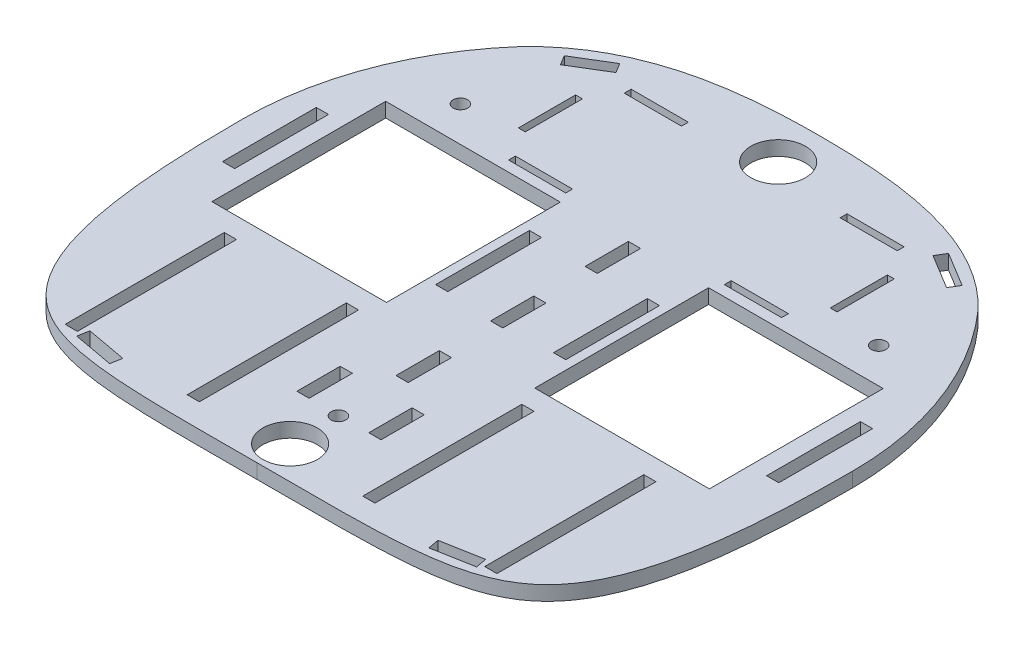
SolidWorks part; units mm, degrees
ref_plane "Front Plane" through (0, 0, 0) normal (0, 0, 1) x (1, 0, 0)
ref_plane "Top Plane" through (0, 0, 0) normal (0, 1, 0) x (1, 0, 0)
ref_plane "Right Plane" through (0, 0, 0) normal (1, 0, 0) x (0, 0, -1)
sketch "Sketch1" plane through (0, 0, 0) normal (0, 1, 0) x (1, 0, 0)
  line L0 (0, 0) -> (-157.9039, -157.9039) construction
  line L1 (0, -127) -> (0, 133.35) construction
  arc A0 (133.35, 0) -> (-133.35, 0) centre (0, 0) ccw
  spline S0 degree 3 poles (-133.35, 0) (-133.35, -51.198) (-123.8034, -129.8051) (-58.428, -127) (0, -127) knots 0 0 0 0 0.502616 1 1 1 1
  spline S1 degree 3 poles (133.35, 0) (133.35, -51.198) (123.8034, -129.8051) (58.428, -127) (0, -127) knots 0 0 0 0 0.502616 1 1 1 1
  dimension "D1" = 266.7
extrude "Base" add sketch "Sketch1" along normal blind 6.35
sketch "ShaftLayout" plane through (0, 6.35, 0) normal (0, 1, 0) x (1, 0, 0)
  line L0 (-133.35, 0) -> (133.35, 0) construction
  line L1 (0, 133.35) -> (0, -127) construction
  line L2 (-114.7053, -6.35) -> (-104.7993, -6.35)
  line L3 (-36.3853, -38) -> (-94.3853, -38)
  line L4 (-36.3853, -38) -> (-36.3853, 38)
  line L5 (-36.3853, 38) -> (-94.3853, 38)
  line L6 (-94.3853, -38) -> (-94.3853, 38)
  line L7 (-36.3853, -38) -> (-94.3853, 38) construction
  line L8 (-36.3853, 38) -> (-94.3853, -38) construction
  line L9 (-102.0053, -15.875) -> (-104.7993, -15.875)
  line L10 (-102.0053, -15.875) -> (-102.0053, 15.875)
  line L11 (-102.0053, 15.875) -> (-104.7993, 15.875)
  line L12 (-104.7993, -15.875) -> (-104.7993, 15.875)
  line L13 (-102.0053, -15.875) -> (-104.7993, 15.875) construction
  line L14 (-102.0053, 15.875) -> (-104.7993, -15.875) construction
  line L15 (-114.7053, -6.35) -> (-114.7053, 6.35)
  line L16 (-104.7993, -6.35) -> (-104.7993, 6.35)
  line L17 (-114.7053, 6.35) -> (-104.7993, 6.35)
  line L18 (-114.7053, -6.35) -> (-104.7993, 6.35) construction
  line L19 (-104.7993, -6.35) -> (-114.7053, 6.35) construction
  line L20 (-116.2928, -9.525) -> (-114.7053, -9.525)
  line L21 (-116.2928, -9.525) -> (-116.2928, 9.525)
  line L22 (-114.7053, -9.525) -> (-114.7053, 9.525)
  line L23 (-116.2928, 9.525) -> (-114.7053, 9.525)
  line L24 (-116.2928, -9.525) -> (-114.7053, 9.525) construction
  line L25 (-114.7053, -9.525) -> (-116.2928, 9.525) construction
  line L26 (-127.4053, -7.9375) -> (-116.2928, -7.9375)
  line L27 (-127.4053, -7.9375) -> (-127.4053, 7.9375)
  line L28 (-116.2928, -7.9375) -> (-116.2928, 7.9375)
  line L29 (-127.4053, 7.9375) -> (-116.2928, 7.9375)
  line L30 (-127.4053, -7.9375) -> (-116.2928, 7.9375) construction
  line L31 (-116.2928, -7.9375) -> (-127.4053, 7.9375) construction
  line L32 (-17.3353, -7.9375) -> (-28.4478, -7.9375)
  line L33 (-30.0353, -9.525) -> (-28.4478, -9.525)
  line L34 (-30.0353, -9.525) -> (-30.0353, 9.525)
  line L35 (-30.0353, 9.525) -> (-28.4478, 9.525)
  line L36 (-28.4478, -9.525) -> (-28.4478, 9.525)
  line L37 (-30.0353, -9.525) -> (-28.4478, 9.525) construction
  line L38 (-30.0353, 9.525) -> (-28.4478, -9.525) construction
  line L39 (-17.3353, -7.9375) -> (-17.3353, 7.9375)
  line L40 (-28.4478, -7.9375) -> (-28.4478, 7.9375)
  line L41 (-17.3353, 7.9375) -> (-28.4478, 7.9375)
  line L42 (-17.3353, -7.9375) -> (-28.4478, 7.9375) construction
  line L43 (-28.4478, -7.9375) -> (-17.3353, 7.9375) construction
  line L45 (-67.3853, -10.033) -> (-56.3853, -10.033)
  line L46 (-67.3853, -10.033) -> (-67.3853, 10.033)
  line L47 (-67.3853, 10.033) -> (-56.3853, 10.033)
  line L48 (-56.3853, -10.033) -> (-56.3853, 10.033)
  line L49 (-67.3853, -10.033) -> (-56.3853, 10.033) construction
  line L50 (-67.3853, 10.033) -> (-56.3853, -10.033) construction
  arc A0 (133.35, 0) -> (-133.35, 0) centre (0, 0) ccw construction
  point P10 (-65.3853, 0)
  point P15 (-103.4023, 0)
  point P20 (-29.2416, 0)
  point P21 (-109.7523, 0)
  point P22 (-115.4991, 0)
  point P23 (-121.8491, 0)
  point P40 (-61.8853, 0)
  point P41 (-22.8916, 0)
  dimension "D1" = 58
  dimension "D2" = 76
  dimension "D3" = 7.62
  dimension "D4" = 2.794
  dimension "D5" = 31.75
  dimension "D6" = 9.906
  dimension "D7" = 12.7
  dimension "D8" = 19.05
  dimension "D9" = 1.5875
  dimension "D10" = 12.7
  dimension "D11" = 15.875
  dimension "D12" = 19.05
  dimension "D13" = 1.5875
  dimension "D14" = 15.875
  dimension "D15" = 12.7
  dimension "D16" = 6.35
  dimension "D17" = 20.066
  dimension "D18" = 20
  dimension "D19" = 11
sketch "MotorLayout" plane through (0, 6.35, 0) normal (0, 1, 0) x (1, 0, 0)
  line L0 (-94.3853, -81.74) -> (-114.3853, -81.74) construction
  line L1 (-94.3853, -110.24) -> (-18.3853, -110.24)
  line L2 (-94.3853, -110.24) -> (-94.3853, -53.24)
  line L3 (-94.3853, -53.24) -> (-18.3853, -53.24)
  line L4 (-18.3853, -110.24) -> (-18.3853, -53.24)
  line L5 (-94.3853, -110.24) -> (-18.3853, -53.24) construction
  line L6 (-94.3853, -53.24) -> (-18.3853, -110.24) construction
  line L7 (-114.7053, -92.0587) -> (-104.7993, -92.0587)
  line L8 (-104.7993, -97.615) -> (-102.0053, -97.615)
  line L9 (-104.7993, -97.615) -> (-104.7993, -65.865)
  line L10 (-104.7993, -65.865) -> (-102.0053, -65.865)
  line L11 (-102.0053, -97.615) -> (-102.0053, -65.865)
  line L12 (-104.7993, -97.615) -> (-102.0053, -65.865) construction
  line L13 (-104.7993, -65.865) -> (-102.0053, -97.615) construction
  line L14 (-36.3853, -38) -> (-94.3853, -38) construction
  line L15 (-114.7053, -92.0587) -> (-114.7053, -71.4212)
  line L16 (-104.7993, -92.0587) -> (-104.7993, -71.4212)
  line L17 (-114.7053, -71.4212) -> (-104.7993, -71.4212)
  line L18 (-114.7053, -92.0587) -> (-104.7993, -71.4212) construction
  line L19 (-104.7993, -92.0587) -> (-114.7053, -71.4212) construction
  line L20 (-103.4023, -1000) -> (-103.4023, 49000) construction
  line L21 (-34.8953, -53.24) -> (-34.8953, -110.24) construction
  point P0 (-56.3853, -81.74)
  point P7 (-103.4023, -81.74)
  point P14 (-109.7523, -81.74)
  dimension "D1" = 20
  dimension "D2" = 76
  dimension "D3" = 57
  dimension "D4" = 2.794
  dimension "D5" = 15.24
  dimension "D6" = 31.75
  dimension "D7" = 20.6375
  dimension "D8" = 12.7
  dimension "D9" = 7.62
  dimension "D10" = 16.51
sketch "Sketch6" plane through (0, 6.35, 0) normal (0, 1, 0) x (1, 0, 0)
  line L0 (-36.3853, -38) -> (-36.3853, 38) construction
  line L1 (-32.4166, -38) -> (-108.7681, -38)
  line L2 (-32.4166, -38) -> (-32.4166, 38)
  line L3 (-32.4166, 38) -> (-108.7681, 38)
  line L4 (-108.7681, -38) -> (-108.7681, 38)
  line L5 (-28.4478, -9.525) -> (-28.4478, 9.525) construction
  line L6 (-104.7993, -15.875) -> (-104.7993, 15.875) construction
  line L7 (0, 133.35) -> (0, -127) construction
  line L8 (28.4478, 20.5105) -> (23.1138, -20.5105) construction
  line L9 (28.4478, -20.5105) -> (23.1138, 20.5105) construction
  line L10 (116.2928, 20.5105) -> (121.6268, -20.5105) construction
  line L11 (116.2928, -20.5105) -> (121.6268, 20.5105) construction
  line L12 (-133.35, 0) -> (133.35, 0) construction
  line L13 (-116.2928, -20.5105) -> (-121.6268, -20.5105)
  line L14 (-116.2928, -20.5105) -> (-116.2928, 20.5105)
  line L15 (-116.2928, 20.5105) -> (-121.6268, 20.5105)
  line L16 (-121.6268, -20.5105) -> (-121.6268, 20.5105)
  line L17 (-116.2928, -20.5105) -> (-121.6268, 20.5105) construction
  line L18 (-116.2928, 20.5105) -> (-121.6268, -20.5105) construction
  line L19 (-116.2928, -9.525) -> (-116.2928, 9.525) construction
  line L20 (-127.4053, 7.9375) -> (-116.2928, 7.9375) construction
  line L21 (-17.3353, 7.9375) -> (-28.4478, 7.9375) construction
  line L22 (-28.4478, -20.5105) -> (-23.1138, -20.5105)
  line L23 (-28.4478, -20.5105) -> (-28.4478, 20.5105)
  line L24 (-28.4478, 20.5105) -> (-23.1138, 20.5105)
  line L25 (-23.1138, -20.5105) -> (-23.1138, 20.5105)
  line L26 (-28.4478, -20.5105) -> (-23.1138, 20.5105) construction
  line L27 (-28.4478, 20.5105) -> (-23.1138, -20.5105) construction
  line L28 (23.1138, -20.5105) -> (23.1138, 20.5105)
  line L29 (28.4478, 20.5105) -> (23.1138, 20.5105)
  line L30 (28.4478, -20.5105) -> (28.4478, 20.5105)
  line L31 (28.4478, -20.5105) -> (23.1138, -20.5105)
  line L32 (121.6268, -20.5105) -> (121.6268, 20.5105)
  line L33 (116.2928, 20.5105) -> (121.6268, 20.5105)
  line L34 (116.2928, -20.5105) -> (116.2928, 20.5105)
  line L35 (116.2928, -20.5105) -> (121.6268, -20.5105)
  line L36 (108.7681, -38) -> (108.7681, 38)
  line L37 (32.4166, 38) -> (108.7681, 38)
  line L38 (32.4166, -38) -> (32.4166, 38)
  line L39 (32.4166, -38) -> (108.7681, -38)
  point P16 (-118.9598, 0)
  point P27 (-25.7808, 0)
  point P44 (25.7808, 0)
  point P45 (118.9598, 0)
  dimension "D1" = 3.9688
  dimension "D2" = 3.9688
  dimension "D3" = 12.573
  dimension "D4" = 12.573
  dimension "D5" = 5.334
  dimension "D6" = 5.334
extrude "WheelShaftCut" cut sketch "Sketch6" against normal through all
sketch "Sketch8" plane through (0, 6.35, 0) normal (0, 1, 0) x (1, 0, 0)
  line L0 (-94.3853, -81.74) -> (-18.3853, -81.74) construction
  line L1 (-18.3853, -110.24) -> (-18.3853, -53.24) construction
  line L2 (-94.3853, -53.24) -> (-18.3853, -53.24) construction
  line L3 (-35.7113, -116.5265) -> (-41.0453, -116.5265)
  line L4 (-35.7113, -116.5265) -> (-35.7113, -46.9535)
  line L5 (-35.7113, -46.9535) -> (-41.0453, -46.9535)
  line L6 (-41.0453, -116.5265) -> (-41.0453, -46.9535)
  line L7 (-35.7113, -116.5265) -> (-41.0453, -46.9535) construction
  line L8 (-35.7113, -46.9535) -> (-41.0453, -116.5265) construction
  line L9 (18.3853, -72.2785) -> (13.0513, -91.2015) construction
  line L10 (18.3853, -91.2015) -> (13.0513, -72.2785) construction
  line L11 (18.3853, -81.74) -> (15.7183, -81.74) construction
  line L12 (89.0513, -46.9535) -> (94.3853, -116.5265) construction
  line L13 (89.0513, -116.5265) -> (94.3853, -46.9535) construction
  line L14 (35.7113, -46.9535) -> (41.0453, -116.5265) construction
  line L15 (-89.0513, -116.5265) -> (-94.3853, -116.5265)
  line L16 (-89.0513, -116.5265) -> (-89.0513, -46.9535)
  line L17 (-89.0513, -46.9535) -> (-94.3853, -46.9535)
  line L18 (-94.3853, -116.5265) -> (-94.3853, -46.9535)
  line L19 (-89.0513, -116.5265) -> (-94.3853, -46.9535) construction
  line L20 (-89.0513, -46.9535) -> (-94.3853, -116.5265) construction
  line L21 (-94.3853, -110.24) -> (-94.3853, -53.24) construction
  line L22 (0, 133.35) -> (0, -127) construction
  line L23 (35.7113, -116.5265) -> (41.0453, -46.9535) construction
  line L24 (94.3853, -81.74) -> (18.3853, -81.74) construction
  line L25 (13.0513, -91.2015) -> (13.0513, -72.2785)
  line L26 (18.3853, -72.2785) -> (13.0513, -72.2785)
  line L27 (18.3853, -91.2015) -> (18.3853, -72.2785)
  line L28 (18.3853, -91.2015) -> (13.0513, -91.2015)
  line L29 (94.3853, -116.5265) -> (94.3853, -46.9535)
  line L30 (89.0513, -46.9535) -> (94.3853, -46.9535)
  line L31 (89.0513, -116.5265) -> (89.0513, -46.9535)
  line L32 (89.0513, -116.5265) -> (94.3853, -116.5265)
  line L33 (41.0453, -116.5265) -> (41.0453, -46.9535)
  line L34 (35.7113, -46.9535) -> (41.0453, -46.9535)
  line L35 (35.7113, -116.5265) -> (35.7113, -46.9535)
  line L36 (35.7113, -116.5265) -> (41.0453, -116.5265)
  line L37 (-94.3853, -110.24) -> (-18.3853, -110.24) construction
  line L42 (-18.3853, -81.74) -> (-15.7183, -81.74) construction
  line L44 (-18.3853, -91.2015) -> (-13.0513, -91.2015)
  line L45 (-18.3853, -91.2015) -> (-18.3853, -72.2785)
  line L46 (-18.3853, -72.2785) -> (-13.0513, -72.2785)
  line L47 (-13.0513, -91.2015) -> (-13.0513, -72.2785)
  line L48 (-18.3853, -91.2015) -> (-13.0513, -72.2785) construction
  line L49 (-18.3853, -72.2785) -> (-13.0513, -91.2015) construction
  point P6 (-63.7079, -81.74)
  point P7 (-38.2513, -81.74)
  point P19 (-91.5913, -81.74)
  point P39 (91.5913, -81.74)
  point P40 (38.2513, -81.74)
  dimension "D1" = 5.334
  dimension "D2" = 6.2865
  dimension "D4" = 5.334
  dimension "D5" = 18.923
  dimension "D6" = 6.2865
  dimension "D3" = 2
extrude "MotorCut" cut sketch "Sketch8" against normal through all
sketch "BatteryLayout" plane through (0, 6.35, 0) normal (0, 1, 0) x (1, 0, 0)
  line L0 (0, 133.35) -> (0, -127) construction
  line L1 (-32.4166, 38) -> (-108.7681, 38) construction
  line L2 (-66.675, 45.62) -> (66.675, 45.62)
  line L3 (-66.675, 45.62) -> (-66.675, 93.245)
  line L4 (-66.675, 93.245) -> (66.675, 93.245)
  line L5 (66.675, 45.62) -> (66.675, 93.245)
  line L6 (-66.675, 45.62) -> (66.675, 93.245) construction
  line L7 (-66.675, 93.245) -> (66.675, 45.62) construction
  arc A0 (133.35, 0) -> (-133.35, 0) centre (0, 0) ccw construction
  point P6 (0, 69.4325)
  dimension "D1" = 133.35
  dimension "D2" = 47.625
  dimension "D3" = 7.62
sketch "Sketch10" plane through (0, 6.35, 0) normal (0, 1, 0) x (1, 0, 0)
  line L0 (-66.675, 93.245) -> (66.675, 93.245) construction
  line L1 (-59.69, 42.62) -> (-34.69, 42.62)
  line L2 (-59.69, 42.62) -> (-59.69, 45.62)
  line L3 (-59.69, 45.62) -> (-34.69, 45.62)
  line L4 (-34.69, 42.62) -> (-34.69, 45.62)
  line L5 (-59.69, 42.62) -> (-34.69, 45.62) construction
  line L6 (-59.69, 45.62) -> (-34.69, 42.62) construction
  line L7 (-59.69, 96.245) -> (-34.69, 96.245)
  line L8 (-59.69, 96.245) -> (-59.69, 93.245)
  line L9 (-59.69, 93.245) -> (-34.69, 93.245)
  line L10 (-34.69, 96.245) -> (-34.69, 93.245)
  line L11 (-59.69, 96.245) -> (-34.69, 93.245) construction
  line L12 (-59.69, 93.245) -> (-34.69, 96.245) construction
  line L13 (-66.675, 45.62) -> (66.675, 45.62) construction
  line L14 (-66.675, 45.62) -> (-66.675, 93.245) construction
  line L15 (0, 69.4325) -> (-66.675, 69.4325) construction
  line L16 (-66.675, 56.9325) -> (-69.675, 56.9325)
  line L17 (-66.675, 56.9325) -> (-66.675, 81.9325)
  line L18 (-66.675, 81.9325) -> (-69.675, 81.9325)
  line L19 (-69.675, 56.9325) -> (-69.675, 81.9325)
  line L20 (0, 133.35) -> (0, -127) construction
  line L21 (59.69, 93.245) -> (34.69, 96.245) construction
  line L22 (59.69, 96.245) -> (34.69, 93.245) construction
  line L23 (59.69, 45.62) -> (34.69, 42.62) construction
  line L24 (59.69, 42.62) -> (34.69, 45.62) construction
  line L25 (69.675, 56.9325) -> (69.675, 81.9325)
  line L26 (66.675, 81.9325) -> (69.675, 81.9325)
  line L27 (66.675, 56.9325) -> (66.675, 81.9325)
  line L28 (66.675, 56.9325) -> (69.675, 56.9325)
  line L29 (34.69, 96.245) -> (34.69, 93.245)
  line L30 (59.69, 93.245) -> (34.69, 93.245)
  line L31 (59.69, 96.245) -> (59.69, 93.245)
  line L32 (59.69, 96.245) -> (34.69, 96.245)
  line L33 (34.69, 42.62) -> (34.69, 45.62)
  line L34 (59.69, 45.62) -> (34.69, 45.62)
  line L35 (59.69, 42.62) -> (59.69, 45.62)
  line L36 (59.69, 42.62) -> (34.69, 42.62)
  point P0 (-47.19, 44.12)
  point P5 (-47.19, 94.745)
  point P20 (-66.675, 69.4325)
  point P40 (66.675, 69.4325)
  point P41 (47.19, 94.745)
  point P42 (47.19, 44.12)
  dimension "D1" = 3
  dimension "D2" = 3
  dimension "D3" = 25
  dimension "D4" = 25
  dimension "D5" = 6.985
  dimension "D6" = 6.985
  dimension "D7" = 3
  dimension "D8" = 25
extrude "VelcroCut" cut sketch "Sketch10" against normal through all
sketch "Sketch11" plane through (0, 6.35, 0) normal (0, 1, 0) x (1, 0, 0)
  line L0 (0, 133.35) -> (0, -127) construction
  line L1 (-133.35, 0) -> (133.35, 0) construction
  circle A1 centre (0, -91.44) radius 3.175
  circle A2 centre (-91.44, 53.34) radius 3.175
  circle A3 centre (91.44, 53.34) radius 3.175
  dimension "D1" = 6.35
  dimension "D2" = 53.34
  dimension "D3" = 6.35
  dimension "D6" = 91.44
  dimension "D4" = 91.44
extrude "ScrewCut" cut sketch "Sketch11" against normal through all
sketch "Sketch13" plane through (0, 6.35, 0) normal (0, 1, 0) x (1, 0, 0)
  line L0 (0, 133.35) -> (0, -127) construction
  line L1 (-2.667, 19.077) -> (2.667, 19.077)
  line L2 (-2.667, 19.077) -> (-2.667, 38)
  line L3 (-2.667, 38) -> (2.667, 38)
  line L4 (2.667, 19.077) -> (2.667, 38)
  line L5 (-2.667, 19.077) -> (2.667, 38) construction
  line L6 (-2.667, 38) -> (2.667, 19.077) construction
  line L7 (108.7681, 38) -> (32.4166, 38) construction
  line L8 (-2.667, -22.2615) -> (2.667, -22.2615)
  line L9 (-2.667, -22.2615) -> (-2.667, -3.3385)
  line L10 (-2.667, -3.3385) -> (2.667, -3.3385)
  line L11 (2.667, -22.2615) -> (2.667, -3.3385)
  line L12 (-2.667, -22.2615) -> (2.667, -3.3385) construction
  line L13 (-2.667, -3.3385) -> (2.667, -22.2615) construction
  line L14 (-2.667, -63.6) -> (2.667, -63.6)
  line L15 (-2.667, -63.6) -> (-2.667, -44.677)
  line L16 (-2.667, -44.677) -> (2.667, -44.677)
  line L17 (2.667, -63.6) -> (2.667, -44.677)
  line L18 (-2.667, -63.6) -> (2.667, -44.677) construction
  line L19 (-2.667, -44.677) -> (2.667, -63.6) construction
  point P0 (0, 28.5385)
  point P10 (0, -12.8)
  point P15 (0, -54.1385)
  dimension "D1" = 5.334
  dimension "D2" = 18.923
  dimension "D3" = 0
  dimension "D5" = 101.6
  dimension "D4" = 3
extrude "SupportStrutCut" cut sketch "Sketch13" against normal through all
sketch "Sketch16" plane through (0, 6.35, 0) normal (0, 1, 0) x (1, 0, 0)
  line L0 (0, -1000) -> (0, 49000) construction
  line L1 (-100.0331, 133.35) -> (-100.0331, 88.1793)
  line L2 (-100.0331, 133.35) -> (100.0331, 133.35)
  line L3 (100.0331, 133.35) -> (100.0331, 88.1793)
  arc A0 (133.35, 0) -> (-133.35, 0) centre (0, 0) ccw construction
  spline S0 degree 3 poles (-100.0331, 88.1793) (-73.9195, 115.9102) (-34.9729, 119.8228) (0, 119.8228) knots 0 0 0 0 1 1 1 1
  spline S1 degree 3 poles (100.0331, 88.1793) (73.9195, 115.9102) (34.9729, 119.8228) (0, 119.8228) knots 0 0 0 0 1 1 1 1
extrude "EmptySpaceTrim" cut sketch "Sketch16" against normal through all
sketch "Sketch15" plane through (0, 6.35, 0) normal (0, 1, 0) x (1, 0, 0)
  line L0 (-78.1477, -1116.59) -> (-78.1477, 48883.41) construction
  line L2 (-87.4187, -118.4593) -> (-69.7657, -121.6799)
  line L3 (-87.4187, -118.4593) -> (-86.5298, -113.5867)
  line L4 (-69.7657, -121.6799) -> (-68.8768, -116.8073)
  line L5 (-86.5298, -113.5867) -> (-68.8768, -116.8073)
  line L6 (-87.4187, -118.4593) -> (-68.8768, -116.8073) construction
  line L7 (-69.7657, -121.6799) -> (-86.5298, -113.5867) construction
  line L8 (-84.4066, 90.0604) -> (-69.3179, 99.2234)
  line L9 (-84.4066, 90.0604) -> (-86.9775, 94.2939)
  line L10 (-69.3179, 99.2234) -> (-71.8889, 103.4569)
  line L11 (-86.9775, 94.2939) -> (-71.8889, 103.4569)
  line L12 (-84.4066, 90.0604) -> (-71.8889, 103.4569) construction
  line L13 (-69.3179, 99.2234) -> (-86.9775, 94.2939) construction
  line L14 (0, -1000) -> (0, 49000) construction
  line L15 (69.3179, 99.2234) -> (86.9775, 94.2939) construction
  line L16 (84.4066, 90.0604) -> (71.8889, 103.4569) construction
  line L17 (69.7657, -121.6799) -> (86.5298, -113.5867) construction
  line L18 (87.4187, -118.4593) -> (68.8768, -116.8073) construction
  line L19 (88.7973, -116.59) -> (66.5019, -116.59) construction
  line L20 (86.9775, 94.2939) -> (71.8889, 103.4569)
  line L21 (69.3179, 99.2234) -> (71.8889, 103.4569)
  line L22 (84.4066, 90.0604) -> (86.9775, 94.2939)
  line L23 (84.4066, 90.0604) -> (69.3179, 99.2234)
  line L24 (86.5298, -113.5867) -> (68.8768, -116.8073)
  line L25 (69.7657, -121.6799) -> (68.8768, -116.8073)
  line L26 (87.4187, -118.4593) -> (86.5298, -113.5867)
  line L27 (87.4187, -118.4593) -> (69.7657, -121.6799)
  point P4 (-78.1477, 96.7587)
  point P7 (-78.1477, -117.6333)
  point P30 (78.1477, -117.6333)
  point P31 (78.1477, 96.7587)
  dimension "D1" = 4.953
  dimension "D2" = 17.653
  dimension "D3" = 17.653
  dimension "D4" = 4.953
extrude "TapeSensorCut" cut sketch "Sketch15" against normal through all
sketch "Sketch17" plane through (0, 6.35, 0) normal (0, 1, 0) x (1, 0, 0)
  line L0 (0, -1000) -> (0, 49000) construction
  line L1 (-34.69, 93.245) -> (34.69, 93.245) construction
  circle A0 centre (0, 100.8346) radius 11.938
  circle A1 centre (0, 100.8346) radius 5 construction
  circle A2 centre (0, -112.5625) radius 11.938
  dimension "D1" = 23.876
  dimension "D2" = 10
  dimension "D3" = 23.876
extrude "CasterCut" cut sketch "Sketch17" against normal through all
sketch "Layer1Limits" plane through (0, 0, 0) normal (0, 1, 0) x (1, 0, 0)
  line L0 (-127, 119.8228) -> (127, -134.1772) construction
  line L1 (-127, -134.1772) -> (127, -134.1772) construction
  line L2 (-127, -134.1772) -> (-127, 119.8228) construction
  line L3 (-127, 119.8228) -> (127, 119.8228) construction
  line L4 (127, -134.1772) -> (127, 119.8228) construction
  line L5 (127, 119.8228) -> (-127, -134.1772) construction
  line L6 (0, -1000) -> (0, 49000) construction
  point P4 (0, -7.1772)
  dimension "D1" = 254
  dimension "D2" = 254
